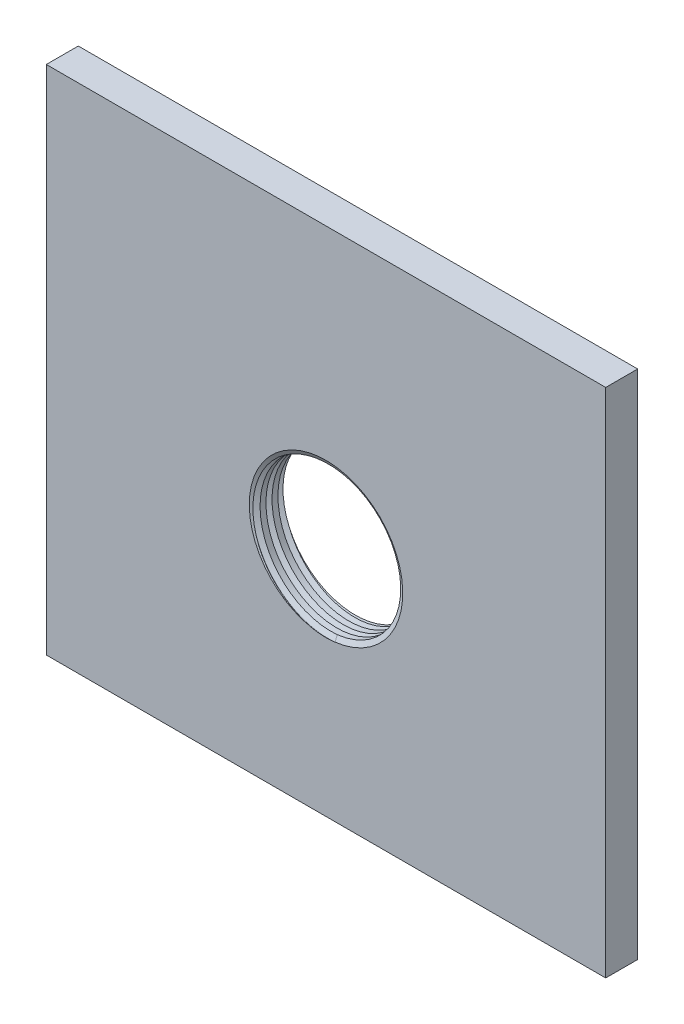
SolidWorks part; units mm, degrees
ref_plane "Front Plane" through (0, 0, 0) normal (0, 0, 1) x (1, 0, 0)
ref_plane "Top Plane" through (0, 0, 0) normal (0, 1, 0) x (1, 0, 0)
ref_plane "Right Plane" through (0, 0, 0) normal (1, 0, 0) x (0, 0, -1)
sketch "Sketch1" plane through (0, 0, 0) normal (0, 0, 1) x (1, 0, 0)
  line L1 (0, 0) -> (35, 0)
  line L2 (0, 0) -> (0, 35)
  line L3 (0, 35) -> (35, 35)
  line L4 (35, 0) -> (35, 35)
  dimension "D1" = 35
  dimension "D2" = 35
extrude "Boss-Extrude1" add sketch "Sketch1" along normal blind 2
sketch "Sketch2" plane through (0, 0, 2) normal (0, 0, 1) x (1, 0, 0)
  circle A0 centre (17.5, 17.5) radius 4.5
  dimension "D1" = 9
extrude "Cut-Extrude1" cut sketch "Sketch2" against normal up to next
sketch "Sketch21" plane through (0, 0, 2) normal (0, 0, 1) x (1, 0, 0)
  circle A0 centre (17.5, 17.5) radius 4.5 construction
  circle A1 centre (17.5, 17.5) radius 4.5
curve "Helix/Spiral8" pitch 0.75 height 2.25 radius 4.5 centre (17.5, 17.5, 2) axis (0, 0, -1) start towards (1, 0, 0)
ref_plane "Plane5" through (0, 17.5, 0) normal (0, -1, 0) x (-1, 0, 0)
sketch "Sketch22" plane through (0, 17.5, 0) normal (0, -1, 0) x (-1, 0, 0)
  line L0 (-35, -2) -> (-35, 0) construction
  line L1 (-22, -2.3822) -> (-22, -2)
  line L2 (-22, -2) -> (-22.301, -2.1738)
  line L3 (-22.301, -2.2084) -> (-22, -2.3822)
  line L4 (-22.2207, -2.1911) -> (-22.2207, -2.2548) construction
  line L5 (-22.2207, -2.1911) -> (-22.2207, -2.1274) construction
  line L7 (-22, -2.1911) -> (-22.311, -2.1911) construction
  circle A0 centre (-22.1103, -2.1911) radius 0.1103 construction
  arc A1 (-22.301, -2.2084) -> (-22.301, -2.1738) centre (-22.291, -2.1911) cw
  dimension "D2" = 0.02
  dimension "D1" = 0.311
sweep "Cut-Sweep9" cut profiles "Sketch22" path "Helix/Spiral8"
sketch "Sketch24" plane through (0, 0, 2) normal (0, 0, 1) x (1, 0, 0)
  circle A0 centre (17.5, 17.5) radius 4.801
extrude "Cut-Extrude2" cut sketch "Sketch24" against normal blind 10 draft 60
sketch "Sketch25" plane through (0, 0, 0) normal (0, 0, -1) x (-1, 0, 0)
  circle A0 centre (-17.5, 17.5) radius 4.801
extrude "Cut-Extrude3" cut sketch "Sketch25" against normal blind 10 draft 60
sketch "Sketch26" plane through (0, 0, 0) normal (0, -1, 0) x (1, 0, 0)
  line L4 (0, 0) -> (35, 0)
  line L5 (35, 0) -> (35, 2)
  line L6 (35, 2) -> (0, 2)
  line L7 (0, 2) -> (0, 0)
  line L8 (0, 0) -> (35, 0)
  line L9 (35, 0) -> (35, 2)
  line L10 (35, 2) -> (0, 2)
  line L11 (0, 2) -> (0, 0)
  dimension "D1" = 0
extrude "Cut-Extrude4" cut sketch "Sketch26" against normal blind 3
